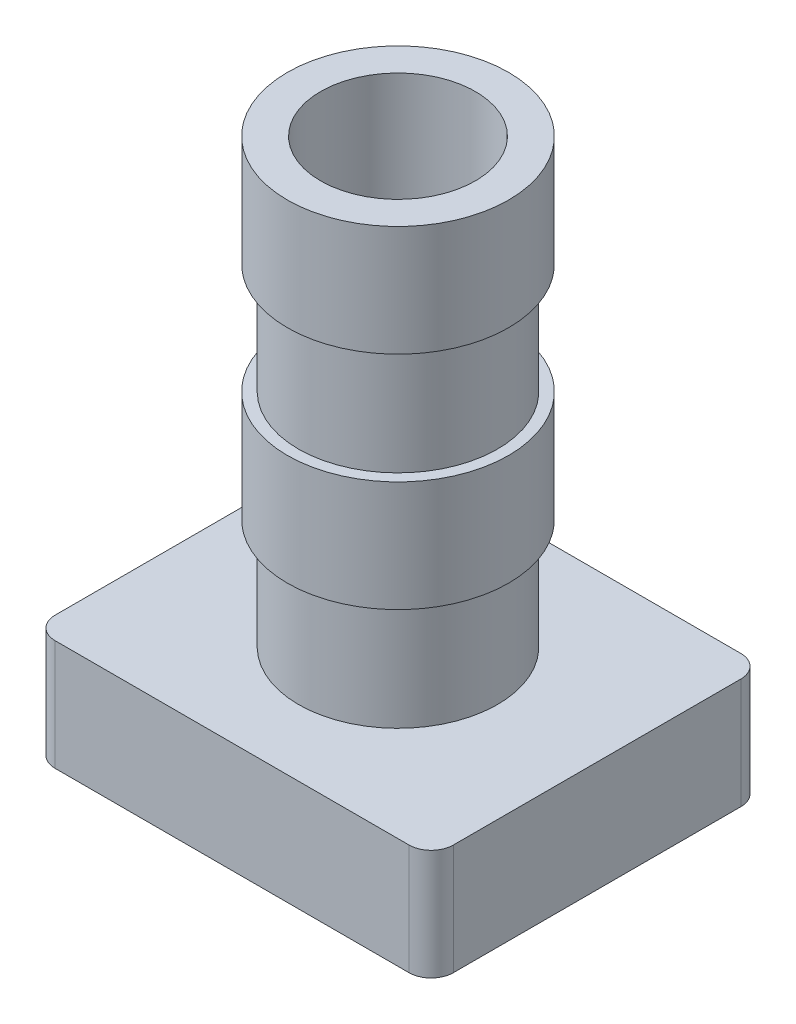
SolidWorks part; units mm, degrees
ref_plane "Front Plane" through (0, 0, 0) normal (0, 0, 1) x (1, 0, 0)
ref_plane "Top Plane" through (0, 0, 0) normal (0, 1, 0) x (1, 0, 0)
ref_plane "Right Plane" through (0, 0, 0) normal (1, 0, 0) x (0, 0, -1)
sketch "Sketch1" plane through (0, 0, 0) normal (0, 1, 0) x (1, 0, 0)
  line L0 (-8.4143, 0) -> (6, 0) construction
  line L1 (0, -5.6176) -> (0, 6.2927) construction
  line L2 (6, -5) -> (6, 5) construction
  line L3 (4.5, -5) -> (4.5, 5)
  line L4 (7.5, -5) -> (7.5, 5)
  line L5 (-6, -5) -> (-6, 5) construction
  line L6 (-4.5, -5) -> (-4.5, 5)
  line L7 (-7.5, -5) -> (-7.5, 5)
  line L9 (-8, 7.5) -> (8, 7.5)
  line L10 (-9, 6.5) -> (-9, -6.5)
  line L11 (-8, -7.5) -> (8, -7.5)
  line L12 (9, 6.5) -> (9, -6.5)
  line L13 (-9, 7.5) -> (9, -7.5) construction
  line L14 (-9, -7.5) -> (9, 7.5) construction
  circle A0 centre (0, 0) radius 4
  arc A1 (4.5, -5) -> (7.5, -5) centre (6, -5) ccw
  arc A2 (7.5, 5) -> (4.5, 5) centre (6, 5) ccw
  arc A3 (-4.5, -5) -> (-7.5, -5) centre (-6, -5) cw
  arc A4 (-7.5, 5) -> (-4.5, 5) centre (-6, 5) cw
  arc A5 (-9, -6.5) -> (-8, -7.5) centre (-8, -6.5) ccw
  arc A6 (-8, 7.5) -> (-9, 6.5) centre (-8, 6.5) ccw
  arc A7 (8, 7.5) -> (9, 6.5) centre (8, 6.5) cw
  arc A8 (8, -7.5) -> (9, -6.5) centre (8, -6.5) ccw
  circle A9 centre (0, 0) radius 4.5
  point P9 (6, 0)
  point P16 (-6, 0)
  dimension "D1" = 8
  dimension "D5" = 1
  dimension "D2" = 3
  dimension "D3" = 10
  dimension "D4" = 12
  dimension "D6" = 18
  dimension "D7" = 15
  dimension "D8" = 0.5
extrude "Boss-Extrude1" add sketch "Sketch1" along normal blind 5 contours L11 A8 L12 A7 L9 A6 L10 A5 A9 L3 A2 L4 A1 L6 A3 L7 A4 | A4 L7 A3 L6 | A9 A0 | A0 | L4 A2 L3 A1 region at (-6, 0, 0) region at (0, 0, 4.3727) region at (6, 0, 0) region at (0, 0, -7.2657) region at (0, 0, 0)
extrude "Cut-Extrude2" cut sketch "Sketch1<5>" along normal through all contours A0 region at (0, 0, 0)
sketch "Sketch1<5>" plane through (0, 0, 0) normal (0, 1, 0) x (1, 0, 0) same geometry as "Sketch1"
extrude "Boss-Extrude4" add sketch "Sketch1<6>" along normal blind 10 contours A9 A0 region at (0, 0, 4.3727)
sketch "Sketch1<6>" plane through (0, 0, 0) normal (0, 1, 0) x (1, 0, 0) same geometry as "Sketch1"
sketch "Sketch3" plane through (0, 10, 0) normal (0, 1, 0) x (1, 0, 0)
  circle A0 centre (0, 0) radius 5
  dimension "D1" = 10
extrude "Boss-Extrude5" add sketch "Sketch3" along normal blind 5
sketch "Sketch4" plane through (0, 15, 0) normal (0, 1, 0) x (1, 0, 0)
  circle A0 centre (0, 0) radius 4.5 construction
  circle A1 centre (0, 0) radius 4.5
extrude "Boss-Extrude6" add sketch "Sketch4" along normal blind 5
sketch "Sketch5" plane through (0, 20, 0) normal (0, 1, 0) x (1, 0, 0)
  circle A0 centre (0, 0) radius 5 construction
  circle A1 centre (0, 0) radius 5
extrude "Boss-Extrude7" add sketch "Sketch5" along normal blind 5
sketch "Sketch6" plane through (0, 25, 0) normal (0, 1, 0) x (1, 0, 0)
  circle A0 centre (0, 0) radius 3.5
  circle A1 centre (0, 0) radius 3
  dimension "D2" = 6
  dimension "D1" = 0.5
extrude "Cut-Extrude3" cut sketch "Sketch6" against normal up to surface (5 mm away) contours A0 A1 | A1 region at (-3.401, 25, 0) up to face at (0, 20, 4.5)
sketch "Sketch7" plane through (0, 10, 0) normal (0, -1, 0) x (1, 0, 0)
  circle A0 centre (0, 0) radius 5 construction
  circle A1 centre (0, 0) radius 5
  circle A2 centre (0, 0) radius 4.5 construction
  circle A3 centre (0, 0) radius 4.5
